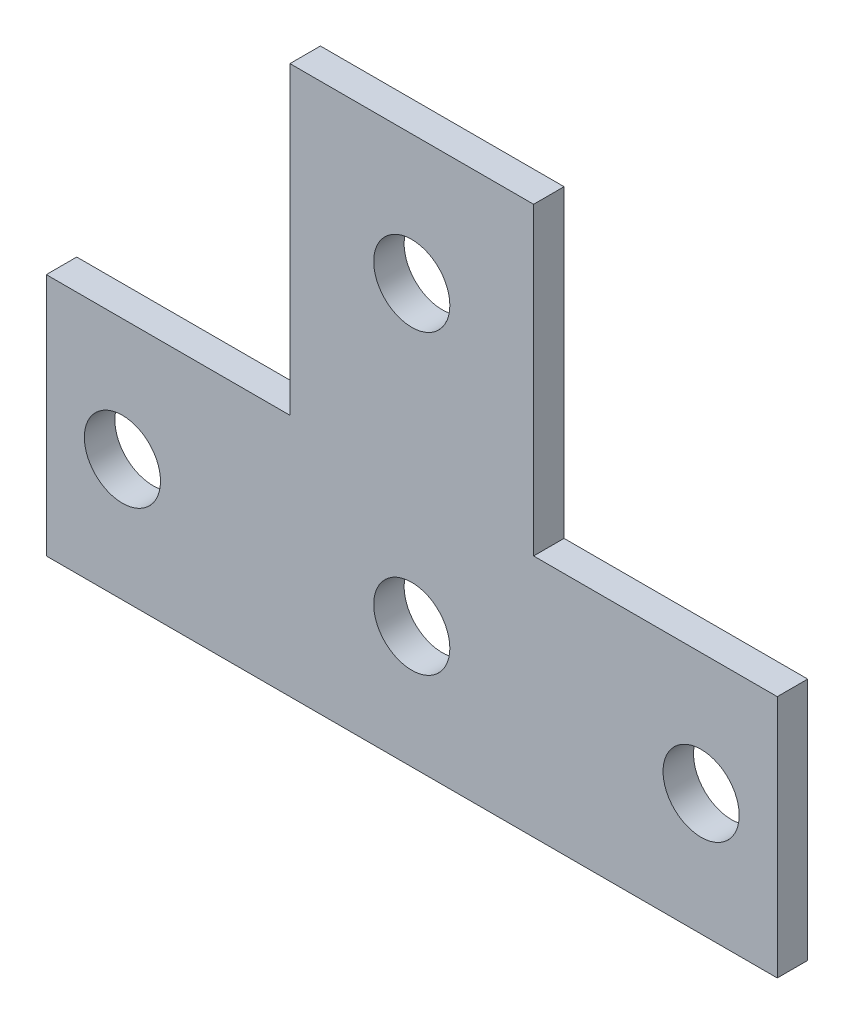
SolidWorks part; units mm, degrees
ref_plane "Front plane" through (0, 0, 0) normal (0, 0, 1) x (1, 0, 0)
ref_plane "Top plane" through (0, 0, 0) normal (0, 1, 0) x (1, 0, 0)
ref_plane "Right plane" through (0, 0, 0) normal (1, 0, 0) x (0, 0, -1)
ref_axis "Axis X" through (0, 0, 0) along (1, 0, 0)
ref_axis "Axis Y" through (0, 0, 0) along (0, 1, 0)
ref_axis "Axis Z" through (0, 0, 0) along (0, 0, 1)
sketch "Sketch2" plane through (0, 0, 0) normal (0, 0, 1) x (1, 0, 0)
  line L0 (-8, 0) -> (-8, 54)
  line L1 (-8, 54) -> (8, 54)
  line L2 (8, 54) -> (8, 0)
  line L3 (8, 0) -> (24, 0)
  line L4 (24, 0) -> (24, -16)
  line L5 (24, -16) -> (-24, -16)
  line L6 (-24, -16) -> (-24, 0)
  line L7 (-24, 0) -> (-8, 0)
  line L8 (0, 54) -> (0, -17.8356) construction
  line L9 (-24, -8) -> (24, -8) construction
  circle A1 centre (19, -8) radius 2.5
  circle A2 centre (0, -8) radius 2.5
  circle A3 centre (-19, -8) radius 2.5
  circle A4 centre (0, 43.75) radius 2.5
  circle A5 centre (0, 11.5) radius 2.5
  dimension "D6" = 5
  dimension "D7" = 5
  dimension "D8" = 5
  dimension "D9" = 5
  dimension "D1" = 48
  dimension "D2" = 70
  dimension "D3" = 16
  dimension "D4" = 16
  dimension "D5" = 5
  dimension "D10" = 10.25
  dimension "D11" = 42.5
extrude "Extrude1" add sketch "Sketch2" along normal blind 2
sketch "Эскиз1" plane through (0, 0, 2) normal (0, 0, 1) x (1, 0, 0)
  line L0 (-8, 20) -> (8, 20)
  line L1 (-8, 54) -> (-8, 0) construction
  line L2 (8, 0) -> (8, 54) construction
  line L3 (-8, 0) -> (-24, 0) construction
  line L4 (-8, 20) -> (-8, 54)
  line L5 (-8, 54) -> (8, 54)
  line L6 (8, 54) -> (8, 20)
  dimension "D1" = 20
extrude "Вырез-Вытянуть1" cut sketch "Эскиз1" against normal through all
